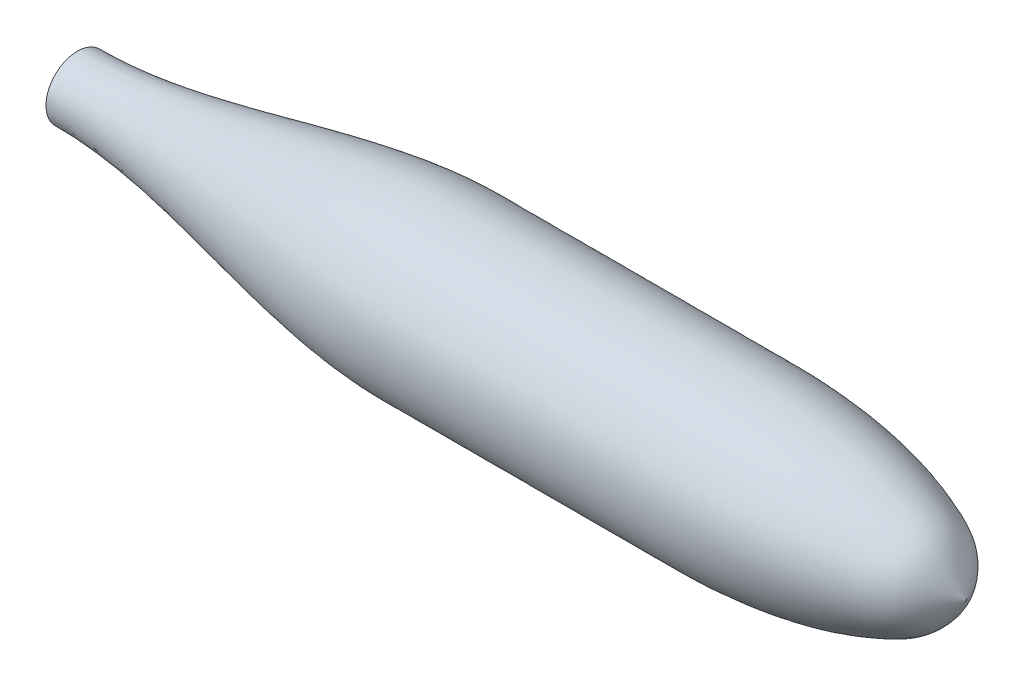
SolidWorks part; units mm, degrees
ref_plane "Front Plane" through (0, 0, 0) normal (0, 0, 1) x (1, 0, 0)
ref_plane "Top Plane" through (0, 0, 0) normal (0, 1, 0) x (1, 0, 0)
ref_plane "Right Plane" through (0, 0, 0) normal (1, 0, 0) x (0, 0, -1)
sketch "Sketch1" plane through (0, 0, 0) normal (0, 0, 1) x (1, 0, 0)
  line L0 (-850, 30) -> (-850, 0)
  line L1 (-850, 0) -> (0, 0)
  line L2 (50, 0) -> (-900, 0) construction
  spline S0 degree 3 poles (0, 0) (-7.9291, 14.788) (-21.0563, 39.2706) (-56.1889, 53.7252) (-84.5565, 63.5782) (-113.1614, 70.2385) (-141.5498, 75.019) (-169.9407, 78.1279) (-198.3092, 79.8747) (-226.6672, 80.0335) (-254.9996, 79.991) (-283.3334, 80.0024) (-311.6666, 79.9993) (-340, 80.0002) (-368.3333, 79.9997) (-396.6667, 80.001) (-424.9999, 79.9964) (-453.3337, 80.0133) (-481.6655, 79.9504) (-510.019, 80.1851) (-538.3981, 78.5839) (-566.7455, 75.4409) (-595.0741, 71.0858) (-623.388, 65.8356) (-651.6931, 60.0084) (-679.9943, 53.9209) (-708.2963, 47.8885) (-736.6039, 42.231) (-764.9222, 37.2521) (-793.2571, 33.3188) (-821.6139, 30.5699) (-840.5493, 30.1897) (-850, 30) knots 0 0 0 0 0.054984 0.09103 0.124986 0.158069 0.190696 0.223064 0.255292 0.287464 0.319634 0.351804 0.383974 0.416144 0.448313 0.480483 0.512653 0.544823 0.576993 0.609163 0.641381 0.67374 0.706279 0.738986 0.771818 0.804711 0.837591 0.870385 0.903036 0.93551 0.967813 1 1 1 1
revolve "Revolve1" add sketch "Sketch1" angle 360 about L2
